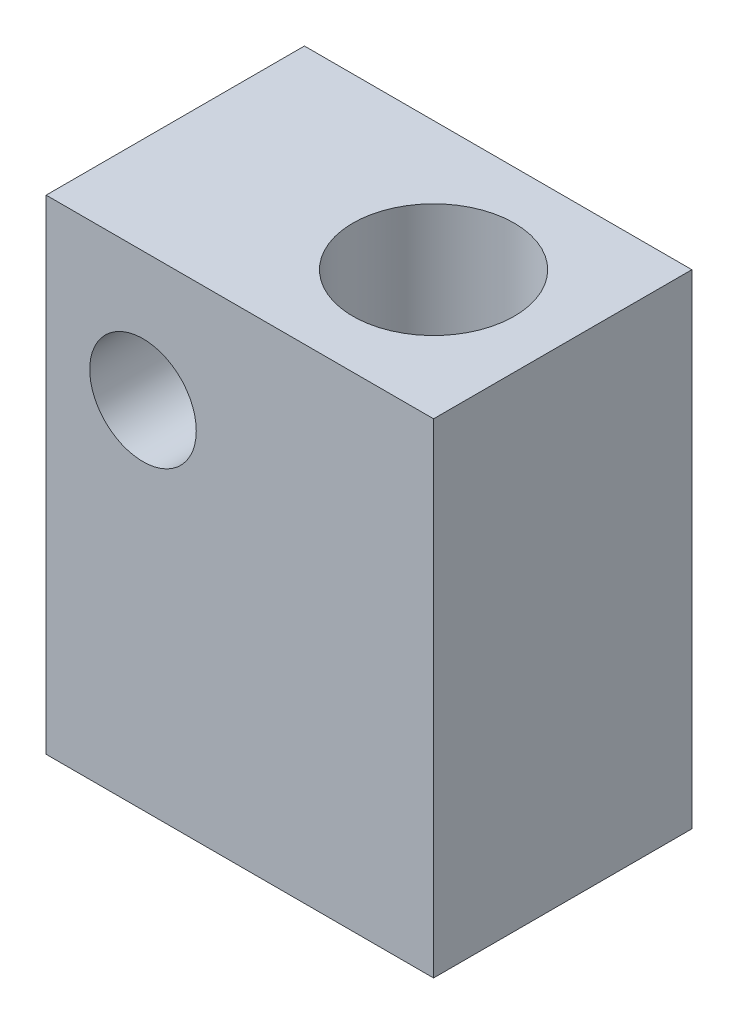
SolidWorks part; units mm, degrees
ref_plane "Front Plane" through (0, 0, 0) normal (0, 0, 1) x (1, 0, 0)
ref_plane "Top Plane" through (0, 0, 0) normal (0, 1, 0) x (1, 0, 0)
ref_plane "Right Plane" through (0, 0, 0) normal (1, 0, 0) x (0, 0, -1)
sketch "Sketch1" plane through (0, 0, 0) normal (0, 0, 1) x (1, 0, 0)
  line L1 (-3, 4) -> (9, 4)
  line L2 (-3, 4) -> (-3, -11)
  line L3 (-3, -11) -> (9, -11)
  line L4 (9, 4) -> (9, -11)
  circle A0 centre (0, 0) radius 1.65
  dimension "D1" = 3.3
  dimension "D2" = 3
  dimension "D3" = 12
  dimension "D4" = 15
  dimension "D5" = 4
extrude "Boss-Extrude1" add sketch "Sketch1" along normal blind 8
sketch "Sketch2" plane through (0, -11, 0) normal (0, -1, 0) x (1, 0, 0)
  line L0 (5, 4) -> (9, 4) construction
  line L1 (9, 8) -> (9, 0) construction
  circle A0 centre (5, 4) radius 2.5
  dimension "D1" = 5
  dimension "D2" = 5
extrude "Cut-Extrude1" cut sketch "Sketch2" against normal through all
sketch "Sketch3" plane through (0, -11, 0) normal (0, -1, 0) x (1, 0, 0)
  circle A0 centre (0, 2.5) radius 1.5
  dimension "D1" = 3
  dimension "D2" = 2.5
extrude "Cut-Extrude2" cut sketch "Sketch3" against normal blind 8
chamfer "Chamfer1" distance 1.25 angle 35.5 1 edges at (0, -3, 1) first distance on face at (0, -3, 1)
